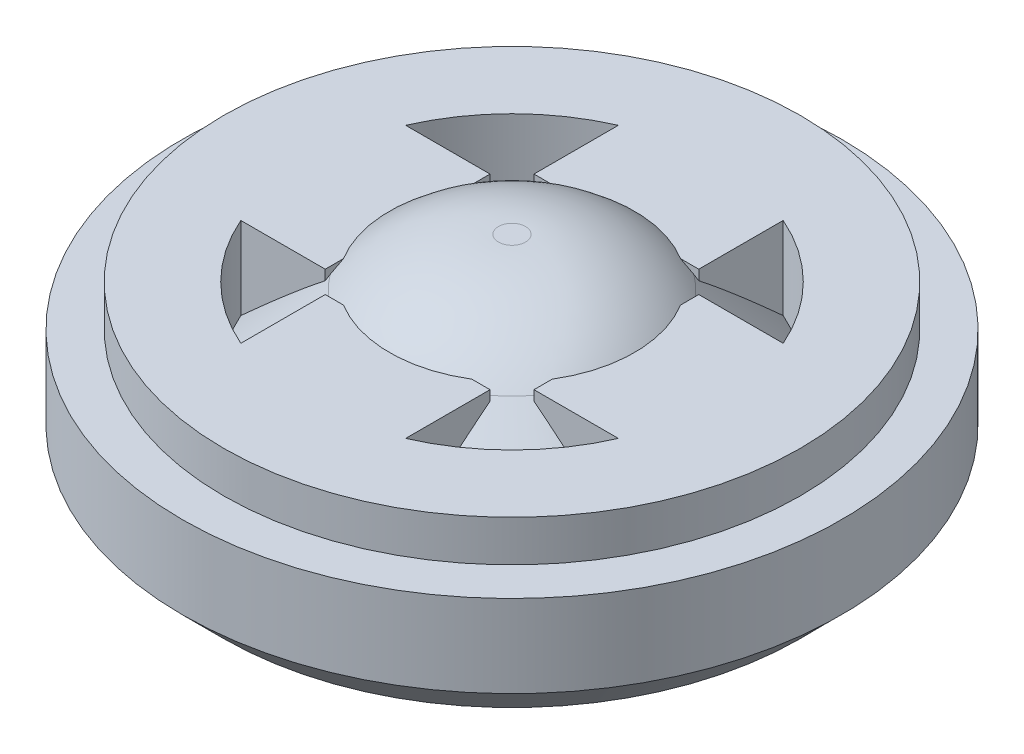
SolidWorks part; units mm, degrees
ref_plane "Front" through (0, 0, 0) normal (0, 0, 1) x (1, 0, 0)
ref_plane "Top" through (0, 0, 0) normal (0, 1, 0) x (1, 0, 0)
ref_plane "Right" through (0, 0, 0) normal (1, 0, 0) x (0, 0, -1)
sketch "草图1" plane through (0, 0, 0) normal (0, 1, 0) x (1, 0, 0)
  circle A0 centre (0, 0) radius 4
  dimension "D1" = 8
extrude "凸台-拉伸1" add sketch "草图1" along normal blind 1
sketch "草图2" plane through (0, 0, 0) normal (0, -1, 0) x (1, 0, 0)
  circle A1 centre (0, 0) radius 1.5
  dimension "D2" = 3
extrude "凸台-拉伸2" add sketch "草图2" along normal blind 0.5
fillet "圆角2" radius 1 1 edges at (0, 0, -1.5)
sketch "草图8" plane through (0, 1, 0) normal (0, 1, 0) x (1, 0, 0)
  circle A0 centre (0, 0) radius 4
  circle A1 centre (0, 0) radius 2.5
  circle A2 centre (0, 0) radius 4 construction
  dimension "D1" = 1.5
extrude "凸台-拉伸3" add sketch "草图8" along normal blind 0.5
sketch "草图14" plane through (0, 1.5, 0) normal (0, 1, 0) x (1, 0, 0)
  circle A0 centre (0, 0) radius 2.5
  circle A1 centre (0, 0) radius 3.5
  circle A3 centre (0, 0) radius 2.5 construction
  dimension "D1" = 1
extrude "凸台-拉伸9" add sketch "草图14" along normal blind 0.5
chamfer "倒角1" distance 0.5 angle 45 1 edges at (0, 0, 4)
sketch "草图15" plane through (0, 1, 0) normal (0, 1, 0) x (1, 0, 0)
  circle A0 centre (0, 0) radius 1
  dimension "D1" = 2
extrude "凸台-拉伸10" add sketch "草图15" along normal blind 1.5
loft "放样1" add section edge at (0, 2.5, 1) section edge at (0, 1, 2.5) connector at (0.3381, 2.5, 0.9411) connector at (1.2995, 1, 2.1357)
sketch "草图13" plane through (0, 0, 0) normal (0, -1, 0) x (1, 0, 0)
  line L0 (0, 17.9095) -> (0, -12.8328) construction
  line L1 (1.2666, 1) -> (1.2666, -1)
  line L2 (-1, 1.2666) -> (1, 1.2666)
  line L3 (-1, 1.2666) -> (-1, 2.8371)
  line L4 (-1, 2.8371) -> (1, 2.8371)
  line L5 (1, 1.2666) -> (1, 2.8371)
  line L6 (-1, 1.2666) -> (1, 2.8371) construction
  line L7 (-1, 2.8371) -> (1, 1.2666) construction
  line L8 (1.2666, 1) -> (2.8371, 1)
  line L9 (2.8371, 1) -> (2.8371, -1)
  line L10 (1.2666, -1) -> (2.8371, -1)
  line L11 (1.2666, 1) -> (2.8371, -1) construction
  line L12 (2.8371, 1) -> (1.2666, -1) construction
  line L13 (1, -1.2666) -> (-1, -1.2666)
  line L14 (1, -1.2666) -> (1, -2.8371)
  line L15 (1, -2.8371) -> (-1, -2.8371)
  line L16 (-1, -1.2666) -> (-1, -2.8371)
  line L17 (1, -1.2666) -> (-1, -2.8371) construction
  line L18 (1, -2.8371) -> (-1, -1.2666) construction
  line L19 (-1.2666, -1) -> (-1.2666, 1)
  line L20 (-1.2666, -1) -> (-2.8371, -1)
  line L21 (-2.8371, -1) -> (-2.8371, 1)
  line L22 (-1.2666, 1) -> (-2.8371, 1)
  line L23 (-1.2666, -1) -> (-2.8371, 1) construction
  line L24 (-2.8371, -1) -> (-1.2666, 1) construction
  point P3 (0, 2.0519)
  point P11 (2.0519, 0)
  point P16 (0, -2.0519)
  point P21 (-2.0519, 0)
  point P26 (0, 0)
  dimension "D1" = 2
  dimension "D2" = 4
extrude "凸台-拉伸8" add sketch "草图13" against normal blind 2
fillet "圆角3" radius 2 1 edges at (0, 2.5, 1)
